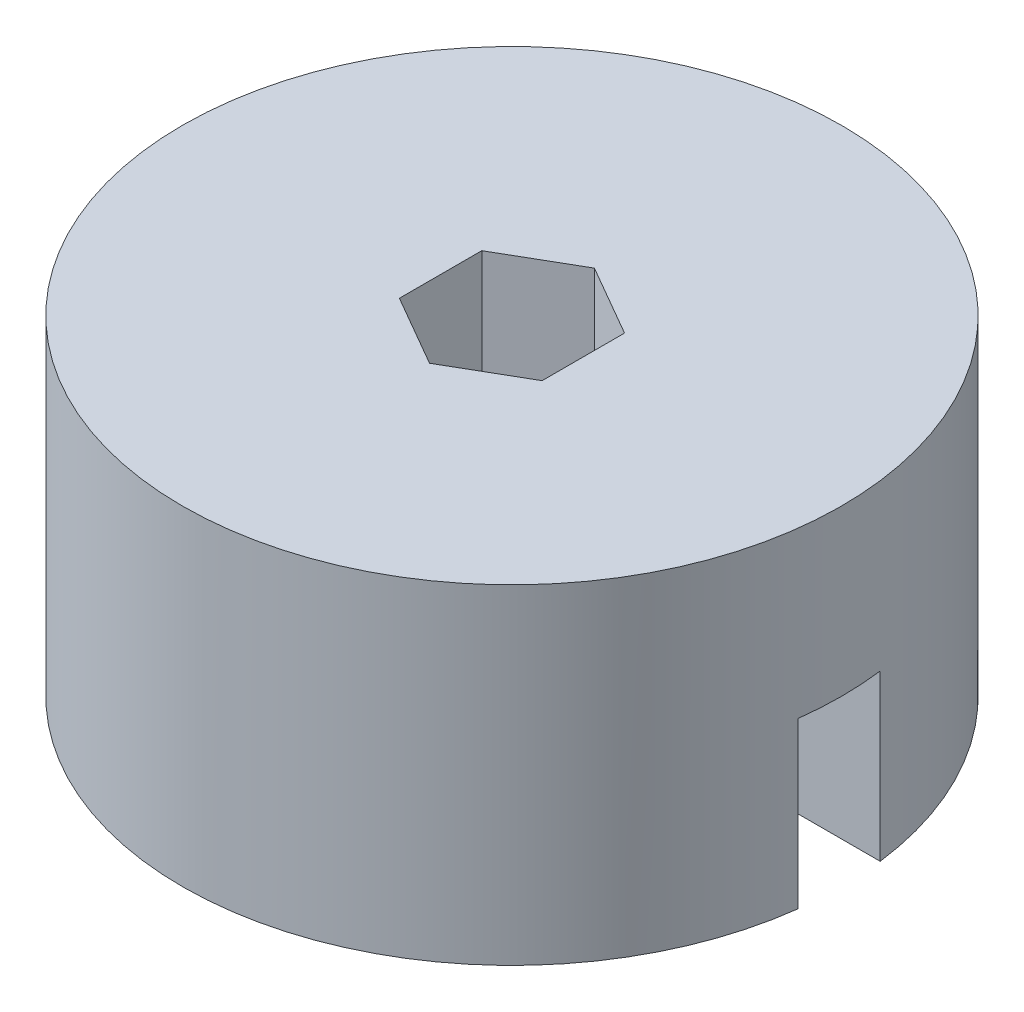
SolidWorks part; units mm, degrees
ref_plane "Front Plane" through (0, 0, 0) normal (0, 0, 1) x (1, 0, 0)
ref_plane "Top Plane" through (0, 0, 0) normal (0, 1, 0) x (1, 0, 0)
ref_plane "Right Plane" through (0, 0, 0) normal (1, 0, 0) x (0, 0, -1)
sketch "Sketch1" plane through (0, 0, 0) normal (0, 1, 0) x (1, 0, 0)
  line L0 (5.4993, 3.175) -> (25.2008, 3.175)
  line L1 (5.4993, -3.175) -> (5.4993, 3.175)
  line L2 (5.4993, 3.175) -> (0, 6.35)
  line L3 (0, 6.35) -> (-5.4993, 3.175)
  line L4 (-5.4993, 3.175) -> (-5.4993, -3.175)
  line L5 (-5.4993, -3.175) -> (0, -6.35)
  line L6 (0, -6.35) -> (5.4993, -3.175)
  line L8 (25.2008, -3.175) -> (5.4993, -3.175)
  circle A0 centre (0, 0) radius 25.4
  circle A1 centre (0, 0) radius 6.35 construction
  dimension "D1" = 50.8
  dimension "D2" = 12.7
extrude "Boss-Extrude1" add sketch "Sketch1" along normal blind 25.4 contours L8 A0 L0 L1 | L0 A0 L8 L6 L5 L4 L3 L2 region at (3.1081, 0, -5.3835) region at (15.4166, 0, 0)
extrude "Cut-Extrude1" cut sketch "Sketch1<4>" along normal blind 12.7 contours L8 A0 L0 L1 region at (15.4166, 0, 0)
sketch "Sketch1<4>" plane through (0, 0, 0) normal (0, 1, 0) x (1, 0, 0) same geometry as "Sketch1"
